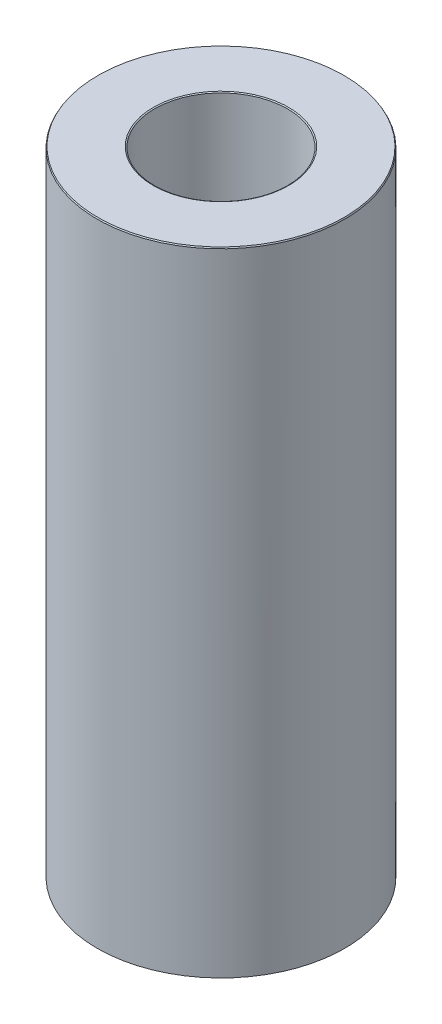
SolidWorks part; units mm, degrees
ref_plane "Front Plane" through (0, 0, 0) normal (0, 0, 1) x (1, 0, 0)
ref_plane "Top Plane" through (0, 0, 0) normal (0, 1, 0) x (1, 0, 0)
ref_plane "Right Plane" through (0, 0, 0) normal (1, 0, 0) x (0, 0, -1)
sketch "Sketch1" plane through (0, 0, 0) normal (0, 1, 0) x (1, 0, 0)
  circle A0 centre (0, 0) radius 50
  dimension "SLEEVE_OD" = 100
extrude "Boss-Extrude1" add sketch "Sketch1" along normal blind 255.9495
sketch "Sketch2" plane through (0, 0, 0) normal (0, 1, 0) x (1, 0, 0)
  circle A0 centre (0, 0) radius 26.8937
  dimension "BORE_D" = 53.7874
extrude "Cut-Extrude1" cut sketch "Sketch2" along normal through all
chamfer "Chamfer1" distance 0.4724 angle 30 4 edges at (0, 255.9495, 26.8937) (0, 0, 26.8937) (0, 0, 50) (0, 255.9495, 50) first distance on face at (0, 255.9495, 26.8937) first distance on face at (0, 0, 26.8937) first distance on face at (0, 255.9495, 50)
